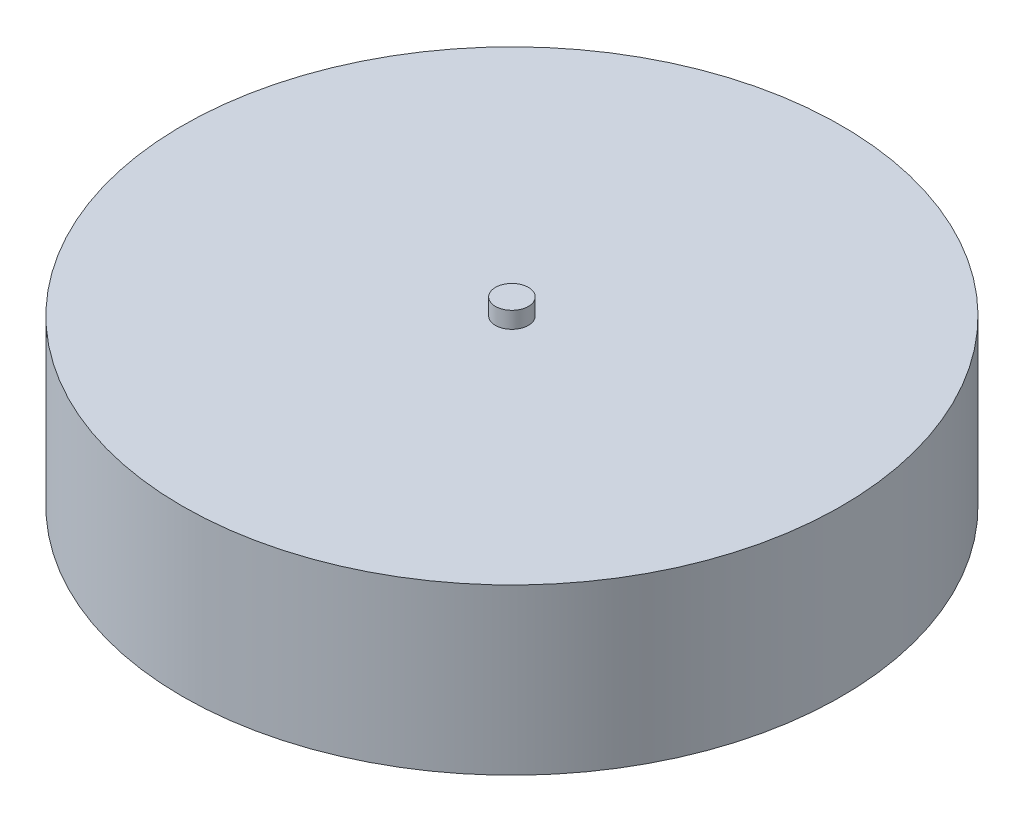
SolidWorks part; units mm, degrees
ref_plane "Front Plane" through (0, 0, 0) normal (0, 0, 1) x (1, 0, 0)
ref_plane "Top Plane" through (0, 0, 0) normal (0, 1, 0) x (1, 0, 0)
ref_plane "Right Plane" through (0, 0, 0) normal (1, 0, 0) x (0, 0, -1)
sketch "Sketch1" plane through (0, 0, 0) normal (0, 1, 0) x (1, 0, 0)
  circle A0 centre (0, 0) radius 200
  circle A1 centre (0, 0) radius 10
  dimension "D1" = 400
extrude "Boss-Extrude1" add sketch "Sketch1" along normal blind 100 contours A0
extrude "Boss-Extrude2" add sketch "Sketch1<3>" along normal blind 110 and the other way blind 10 separate body contours A1
sketch "Sketch1<3>" plane through (0, 0, 0) normal (0, 1, 0) x (1, 0, 0) same geometry as "Sketch1"
